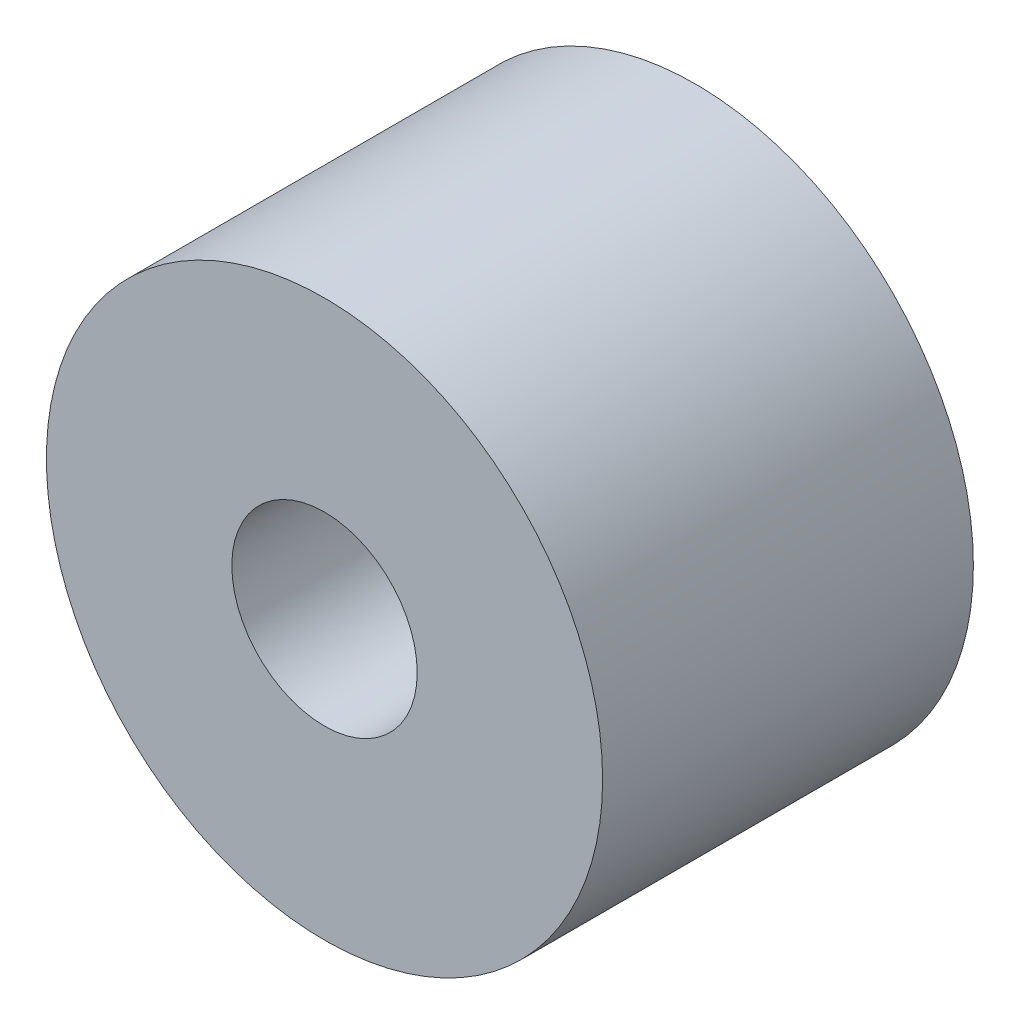
SolidWorks part; units mm, degrees
ref_plane "Front Plane" through (0, 0, 0) normal (0, 0, 1) x (1, 0, 0)
ref_plane "Top Plane" through (0, 0, 0) normal (0, 1, 0) x (1, 0, 0)
ref_plane "Right Plane" through (0, 0, 0) normal (1, 0, 0) x (0, 0, -1)
sketch "Sketch1" plane through (0, 0, 0) normal (0, 0, 1) x (1, 0, 0)
  circle A0 centre (0, 0) radius 15
  circle A1 centre (0, 0) radius 5
  dimension "D1" = 30
  dimension "D2" = 10
extrude "Boss-Extrude1" add sketch "Sketch1" along normal blind 20
ref_plane "Plane1" through (0, 15, 0) normal (0, 1, 0) x (1, 0, 0)
ref_axis "Axis1" through (0, 0, 20) along (0, 0, -1)
ref_plane "Plane2" through (-15, 0, 0) normal (1, 0, 0) x (0, 0, -1)
sketch "Sketch3" plane through (-15, 0, 0) normal (1, 0, 0) x (0, 0, -1)
  line L4 (-5.4421, 4.58) -> (-9.5463, -6.6963)
  line L5 (-9.5463, -6.6963) -> (-12.3654, -5.6702)
  line L6 (-12.3654, -5.6702) -> (-8.2612, 5.6061)
  line L11 (-8.2612, 5.6061) -> (-5.4421, 4.58)
  line L12 (-20, 0) -> (0, 0) construction
  dimension "D1" = 70
  dimension "D2" = 3
  dimension "D3" = 12
sketch "Sketch4" plane through (0, 0, 0) normal (0, 0, -1) x (-1, 0, 0)
  line L0 (0, 0) -> (0, -670) construction
  dimension "D1" = 670
